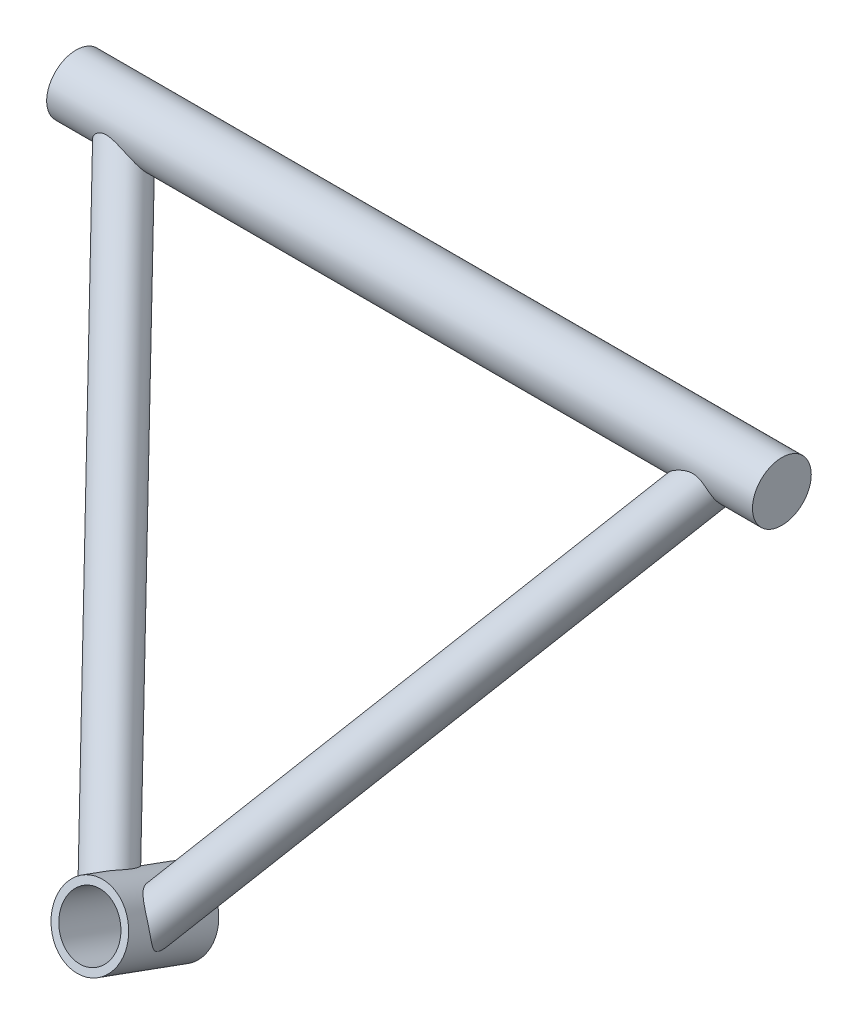
SolidWorks part; units mm, degrees
material "AISI 4130 Steel, normalized at 870C"
ref_plane "Front Plane" through (0, 0, 0) normal (0, 0, 1) x (1, 0, 0)
ref_plane "Top Plane" through (0, 0, 0) normal (0, 1, 0) x (1, 0, 0)
ref_plane "Right Plane" through (0, 0, 0) normal (1, 0, 0) x (0, 0, -1)
sketch "Sketch3" plane through (0, 0, 0) normal (0, 1, 0) x (1, 0, 0)
  line L0 (-5.08, -6.35) -> (5.08, -6.35) construction
  line L2 (0, -88.2205) -> (0, 88.2205) construction
  line L3 (5.08, 0) -> (-5.08, 0) construction
  dimension "D1" = 5.08
  dimension "D2" = 10.16
  dimension "D3" = 6.35
  dimension "D4" = 10.16
  dimension "D5" = 5.08
ref_plane "Plane1" through (0, 3.0668, 3.9968) normal (0, 0.6088, 0.7934) x (1, 0, 0)
ref_plane "Plane3" through (0, 0, 0) normal (0, 0.342, 0.9397) x (-1, 0, 0)
sketch "Sketch1" plane through (0, 0, 0) normal (0, 0.342, 0.9397) x (1, 0, 0)
  circle A0 centre (0, 0) radius 15.875
  dimension "D1" = 31.75
extrude "Boss-Extrude1" add sketch "Sketch1" along normal mid plane 41.402 contours A0
sketch "Sketch4" plane through (0, 3.0668, 3.9968) normal (0, 0.6088, 0.7934) x (1, 0, 0)
  line L0 (-5.08, -3.8656) -> (-132.08, 216.1048)
  line L2 (0, -95.6595) -> (0, 95.6595) construction
  dimension "D2" = 30
  dimension "D3" = 254
sweep "Sweep1" add path "Sketch4" circular profile diameter 19.05 parameters "D3"=19.05
sketch "Sketch15" plane through (0, 3.0668, 3.9968) normal (0, 0.6088, 0.7934) x (1, 0, 0)
  line L0 (5.08, -3.8656) -> (132.08, 216.1048)
  line L1 (0, -95.6595) -> (0, 95.6595) construction
  dimension "D1" = 254
  dimension "D2" = 30
sweep "Sweep2" add path "Sketch15" circular profile diameter 19.05 parameters "D3"=19.05
sketch "Sketch36" plane through (-126.5961, 173.9593, -133.4837) normal (-0.5, 0.6871, -0.5272) x (0.8659, 0.3845, -0.3201)
  circle A0 centre (-6.4312, -4.9109) radius 7.9375
  dimension "D1" = 15.875
extrude "Cut-Extrude2" cut sketch "Sketch36" against normal up to surface (272.7619 mm away) up to face at (14.7605, 3.3964, -7.7533)
sketch "Sketch37" plane through (126.5961, 173.9593, -133.4837) normal (0.5, 0.6871, -0.5272) x (0.8659, -0.3845, 0.3201)
  circle A0 centre (6.4312, -4.9109) radius 7.9375
  dimension "D1" = 15.875
extrude "Cut-Extrude3" cut sketch "Sketch37" against normal up to surface (241.0687 mm away) up to face at (-0.0779, -14.1849, 7.442)
sketch "Sketch77" plane through (0, 7.0802, 19.4526) normal (0, 0.342, 0.9397) x (1, 0, 0)
  circle A1 centre (0, 0) radius 15.875
extrude "Boss-Extrude2" add sketch "Sketch77" against normal up to surface (41.402 mm away) up to face at (0, -21.9978, -14.023)
sketch "Sketch2" plane through (0, -7.0802, -19.4526) normal (0, -0.342, -0.9397) x (-1, 0, 0)
  circle A0 centre (0, 0) radius 12.7
  dimension "D1" = 25.4
extrude "Cut-Extrude1" cut sketch "Sketch2" against normal up to next
ref_plane "Plane2" through (0, 0, -127) normal (0, 0, 1) x (1, 0, 0)
ref_plane "Plane4" through (0, 177.8, 0) normal (0, 1, 0) x (1, 0, 0)
sketch "Sketch40" plane through (-106.934, 0, -127) normal (0, 0, 1) x (1, 0, 0)
  line L0 (108.4431, 172.72) -> (50108.4431, 172.72) construction
  line L1 (-45.466, 172.72) -> (259.334, 172.72)
  point P0 (106.934, 172.72)
  point P1 (106.934, 172.72)
  dimension "D1" = 304.8
  dimension "D5" = 172.72
sweep "Sweep5" add path "Sketch40" circular profile diameter 25.4 parameters "D3"=25.4
sketch "Sketch118" plane through (0, 177.8, 0) normal (0, 1, 0) x (1, 0, 0)
  line L0 (0, 148.2378) -> (-165.1, 148.2378)
  line L1 (0, 148.2378) -> (165.1, 148.2378)
  dimension "D1" = 165.1
  dimension "D2" = 165.1
sweep "Sweep4" [suppressed] add path "Sketch118" circular profile diameter 25.4 parameters "D3"=25.4
